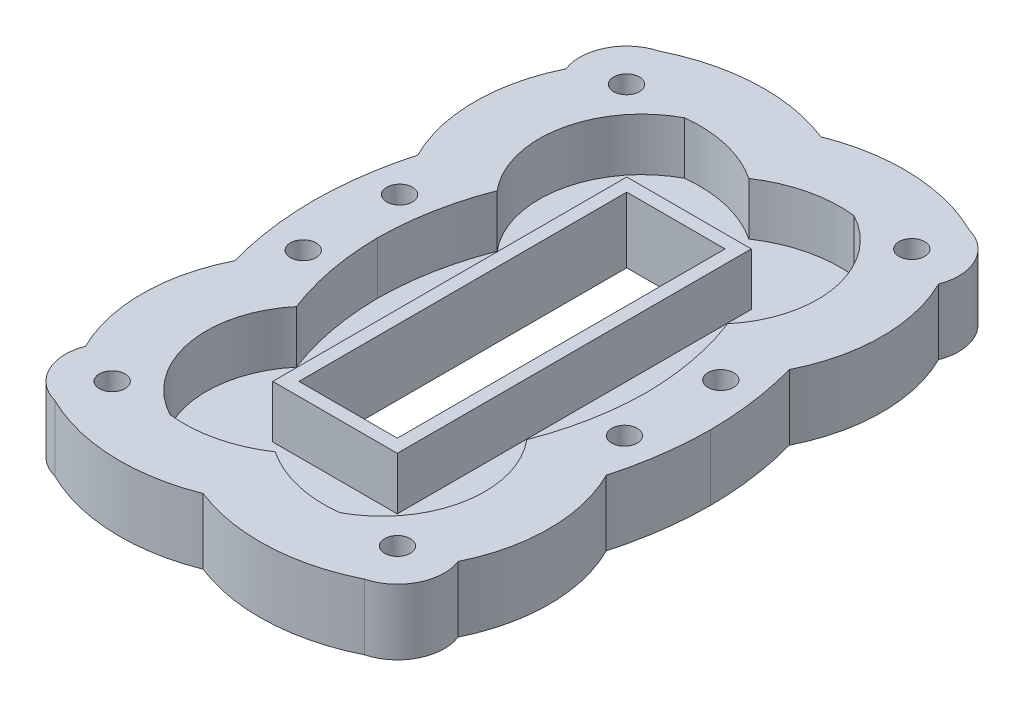
SolidWorks part; units mm, degrees
ref_plane "Front Plane" through (0, 0, 0) normal (0, 0, 1) x (1, 0, 0)
ref_plane "Top Plane" through (0, 0, 0) normal (0, 1, 0) x (1, 0, 0)
ref_plane "Right Plane" through (0, 0, 0) normal (1, 0, 0) x (0, 0, -1)
sketch "Sketch1" plane through (0, 0, 0) normal (0, 1, 0) x (1, 0, 0)
  line L0 (0, -700) -> (0, 700) construction
  line L1 (-700, 0) -> (700, 0) construction
  line L15 (9.5, -27) -> (9.5, 27)
  line L16 (-7.5, -25) -> (7.5, -25)
  line L20 (-7.5, -25) -> (-7.5, 25)
  line L21 (-7.5, 25) -> (7.5, 25)
  line L22 (7.5, -25) -> (7.5, 25)
  line L23 (-7.5, -25) -> (7.5, 25) construction
  line L24 (-7.5, 25) -> (7.5, -25) construction
  line L25 (-9.5, 27) -> (9.5, 27)
  line L26 (-9.5, -27) -> (-9.5, 27)
  line L27 (-9.5, -27) -> (9.5, -27)
  arc A3 (0, 47.1235) -> (23.6031, 46.1331) centre (10.6883, 20.096) cw
  arc A4 (23.6031, 46.1331) -> (28.4233, 36.6485) centre (21.7608, 39.2297) cw
  arc A5 (28.4233, 36.6485) -> (28.3367, 13.9597) centre (5.566, 25.3912) cw
  arc A6 (28.3367, 13.9597) -> (30.2825, 0) centre (-22.8345, -0.2882) cw
  arc A7 (28.3367, -13.9597) -> (30.2825, 0) centre (-22.8345, 0.2882) ccw
  arc A8 (28.4233, -36.6485) -> (28.3367, -13.9597) centre (5.566, -25.3912) ccw
  arc A9 (23.6031, -46.1331) -> (28.4233, -36.6485) centre (21.7608, -39.2297) ccw
  arc A10 (0, -47.1235) -> (23.6031, -46.1331) centre (10.6883, -20.096) ccw
  arc A11 (0, -47.1235) -> (-23.6031, -46.1331) centre (-10.6883, -20.096) cw
  arc A12 (-23.6031, -46.1331) -> (-28.4233, -36.6485) centre (-21.7608, -39.2297) cw
  arc A13 (-28.4233, -36.6485) -> (-28.3367, -13.9597) centre (-5.566, -25.3912) cw
  arc A14 (-28.3367, -13.9597) -> (-30.2825, 0) centre (22.8345, 0.2882) cw
  arc A15 (-28.3367, 13.9597) -> (-30.2825, 0) centre (22.8345, -0.2882) ccw
  arc A16 (-28.4233, 36.6485) -> (-28.3367, 13.9597) centre (-5.566, 25.3912) ccw
  arc A17 (-23.6031, 46.1331) -> (-28.4233, 36.6485) centre (-21.7608, 39.2297) ccw
  arc A18 (0, 47.1235) -> (-23.6031, 46.1331) centre (-10.6883, 20.096) ccw
  arc A41 (-12.9398, 39.2281) -> (-17.5765, 15.3124) centre (-5.566, 25.3912) ccw
  arc A42 (-17.5765, 15.3124) -> (-20.4823, 0) centre (22.8345, -0.2882) ccw
  arc A43 (-17.5765, -15.3124) -> (-20.4823, 0) centre (22.8345, 0.2882) cw
  arc A44 (-12.9398, -39.2281) -> (-17.5765, -15.3124) centre (-5.566, -25.3912) cw
  arc A46 (0, -36.1231) -> (-12.9398, -39.2281) centre (-10.6883, -20.096) cw
  arc A47 (0, -36.1231) -> (12.9398, -39.2281) centre (10.6883, -20.096) ccw
  arc A49 (12.9398, -39.2281) -> (17.5765, -15.3124) centre (5.566, -25.3912) ccw
  arc A50 (17.5765, -15.3124) -> (20.4823, 0) centre (-22.8345, 0.2882) ccw
  arc A51 (17.5765, 15.3124) -> (20.4823, 0) centre (-22.8345, -0.2882) cw
  arc A52 (12.9398, 39.2281) -> (17.5765, 15.3124) centre (5.566, 25.3912) cw
  arc A54 (0, 36.1231) -> (12.9398, 39.2281) centre (10.6883, 20.096) cw
  arc A55 (0, 36.1231) -> (-12.9398, 39.2281) centre (-10.6883, 20.096) ccw
  circle A57 centre (-21.7608, 39.2297) radius 1.96
  circle A58 centre (-24.5, 7.35) radius 1.96
  circle A61 centre (-24.5, -7.35) radius 1.96
  circle A62 centre (-21.7608, -39.2297) radius 1.96
  circle A63 centre (21.7608, -39.2297) radius 1.96
  circle A64 centre (24.5, -7.35) radius 1.96
  circle A65 centre (24.5, 7.35) radius 1.96
  circle A66 centre (21.7608, 39.2297) radius 1.96
  point P7 (0, 0)
  point P8 (0, 0)
  point P81 (0, 0)
  dimension "D1" = 3.92
  dimension "D2" = 29.0642
  dimension "D3" = 7.145
  dimension "D4" = 25.4791
  dimension "D14" = 21.7608
  dimension "D15" = 22.8345
  dimension "D5" = 53.1177
  dimension "D6" = 15.6791
  dimension "D7" = 43.3177
  dimension "D8" = 19.2642
  dimension "D9" = 5.566
  dimension "D10" = 10.6883
  dimension "D11" = 12.9398
  dimension "D12" = 17.5765
  dimension "D13" = 20.4823
  dimension "D16" = 23.6031
  dimension "D17" = 24.5
  dimension "D18" = 7.35
  dimension "D19" = 50
  dimension "D20" = 15
  dimension "D21" = 2
extrude "Boss-Extrude4" add sketch "Sketch1" along normal blind 2 contours A54 A55 A41 A42 A43 A44 A46 A47 A49 A50 A51 A52 L27 region at (-6.402, 0, -37.9585)
extrude "Boss-Extrude7" add sketch "Sketch1<8>" along normal blind 10 contours A3 A18 A17 A16 A15 A14 A13 A12 A11 A10 A9 A8 A7 A6 A5 A4 A65 A64 A63 A61 A58 A57 A55 A54 A52 A51 A50 A49 A47 A46 A44 A43 A42 A41 A62 A66 | L26 L27 L15 L25 L22 L16 L20 L21 region at (0, 0, 26.4275) region at (11.858, 0, -47.9728)
sketch "Sketch1<8>" plane through (0, 0, 0) normal (0, 1, 0) x (1, 0, 0) same geometry as "Sketch1"
